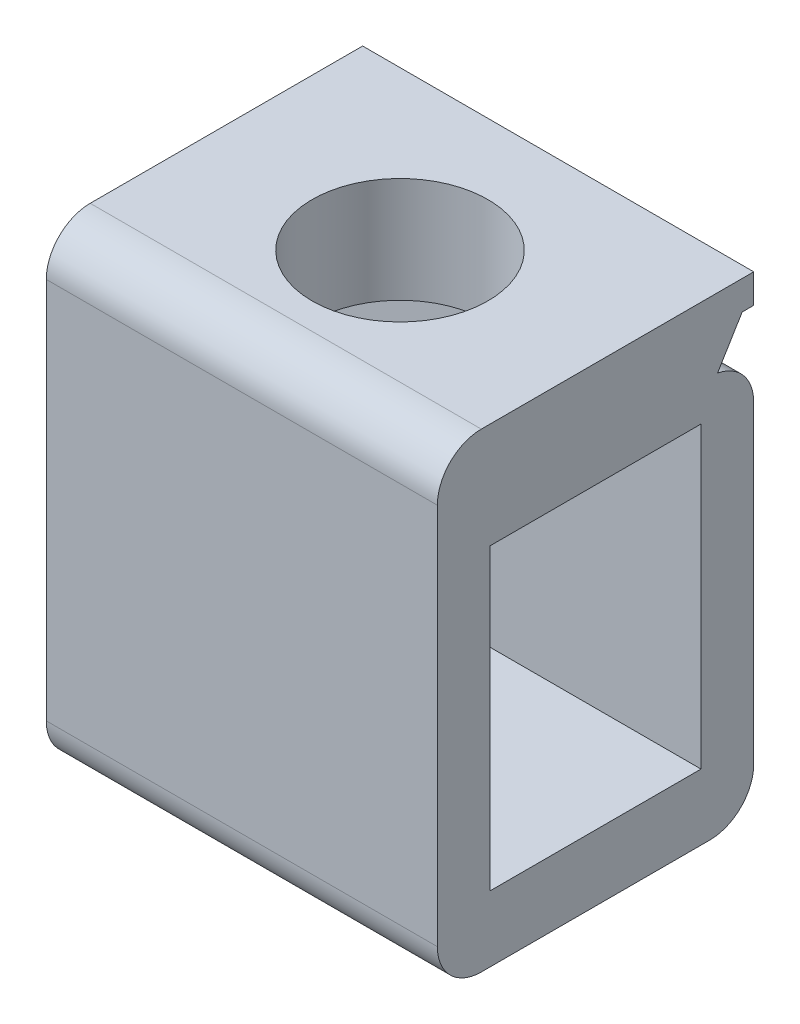
SolidWorks part; units mm, degrees
ref_plane "前视基准面" through (0, 0, 0) normal (0, 0, 1) x (1, 0, 0)
ref_plane "上视基准面" through (0, 0, 0) normal (0, 1, 0) x (1, 0, 0)
ref_plane "右视基准面" through (0, 0, 0) normal (1, 0, 0) x (0, 0, -1)
sketch "草图1" plane through (0, 0, 0) normal (1, 0, 0) x (0, 0, -1)
  line L0 (0, 55.2081) -> (0, -65.0723) construction
  line L1 (-3.6, 5.35) -> (3.6, 5.35)
  line L2 (-3.6, 5.35) -> (-3.6, -5.35)
  line L3 (-3.6, -5.35) -> (3.6, -5.35)
  line L4 (3.6, 5.35) -> (3.6, -5.35)
  line L5 (-64.7541, 0) -> (63.7995, 0) construction
  line L7 (2.4, -3.85) -> (-2.4, -3.85)
  line L8 (2.4, -3.85) -> (2.4, 2.95)
  line L9 (2.4, 2.95) -> (-2.4, 2.95)
  line L10 (-2.4, -3.85) -> (-2.4, 2.95)
  dimension "D1" = 10.7
  dimension "D2" = 7.2
  dimension "D3" = 1.5
  dimension "D4" = 2.4
  dimension "D5" = 1.2
  dimension "D6" = 1.2
extrude "凸台-拉伸1" add sketch "草图1" along normal blind 4.45 and the other way blind 4.45
sketch "草图2" plane through (0, 5.35, 0) normal (0, 1, 0) x (1, 0, 0)
  circle A0 centre (0, 0) radius 2
  dimension "D1" = 4
extrude "切除-拉伸1" cut sketch "草图2" against normal blind 5
sketch "草图3" plane through (4.45, 0, 0) normal (1, 0, 0) x (0, 0, -1)
  line L0 (3.6, 4.6886) -> (3.3369, 4.6886)
  line L2 (3.6, -5.35) -> (3.6, 5.35) construction
  line L3 (3.3369, 4.6886) -> (2.776, 3.7652)
  line L4 (2.776, 3.7652) -> (3.6, 3.7652)
  line L5 (3.6, 3.7652) -> (3.6, 4.6886)
extrude "切除-拉伸2" cut sketch "草图3" against normal up to surface (8.9 mm away) up to face at (-4.45, -0.45, 0)
fillet "圆角1" radius 1 4 edges at (0, -5.35, -3.6) (0, -5.35, 3.6) (0, 5.35, 3.6) (0, 3.7652, -3.6)
